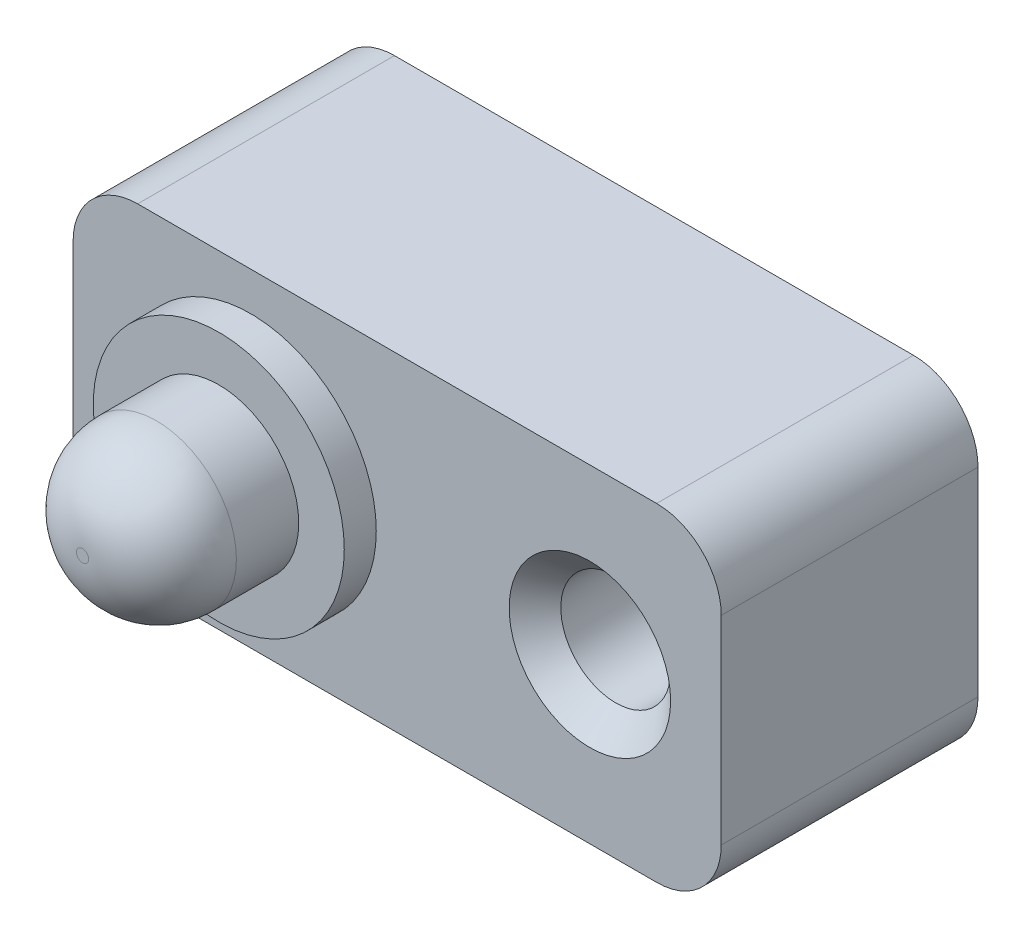
SolidWorks part; units mm, degrees
ref_plane "Front" through (0, 0, 0) normal (0, 0, 1) x (1, 0, 0)
ref_plane "Top" through (0, 0, 0) normal (0, 1, 0) x (1, 0, 0)
ref_plane "Right" through (0, 0, 0) normal (1, 0, 0) x (0, 0, -1)
sketch "Sketch1" plane through (0, 0, 0) normal (0, 0, 1) x (1, 0, 0)
  line L1 (0, 0) -> (20.066, 0)
  line L2 (0, 0) -> (0, 10.16)
  line L3 (0, 10.16) -> (20.066, 10.16)
  line L4 (20.066, 0) -> (20.066, 10.16)
  dimension "D1" = 20.066
  dimension "D2" = 10.16
extrude "Boss-Extrude1" add sketch "Sketch1" along normal blind 7.9502
sketch "Sketch2" plane through (0, 0, 7.9502) normal (0, 0, 1) x (1, 0, 0)
  line L0 (0, 10.16) -> (0, 0) construction
  line L1 (5.5, 10.16) -> (5.5, 0) construction
  line L2 (20.066, 10.16) -> (0, 10.16) construction
  line L3 (0, 0) -> (20.066, 0) construction
  circle A0 centre (5.5, 5.08) radius 3.8862
  dimension "D1" = 7.7724
  dimension "D2" = 5.5
extrude "Boss-Extrude2" add sketch "Sketch2" along normal blind 0.9906
sketch "Sketch3" plane through (0, 0, 8.9408) normal (0, 0, 1) x (1, 0, 0)
  circle A0 centre (5.5, 5.08) radius 2.4765
  dimension "D1" = 4.953
extrude "Boss-Extrude3" add sketch "Sketch3" along normal blind 4.2164
hole_wizard "CSK for M3 SFHCS1" positions "Sketch4" profile "Sketch5" countersink size "M3" standard "ANSI Metric" end condition through all
sketch "Sketch4" plane through (0, 0, 7.9502) normal (0, 0, 1) x (1, 0, 0)
  line L0 (16, 10.16) -> (16, 0) construction
  line L1 (20.066, 10.16) -> (0, 10.16) construction
  line L2 (0, 0) -> (20.066, 0) construction
  circle A0 centre (5.5, 5.08) radius 2.4765 construction
  point P0 (16, 5.08)
  dimension "D1" = 10.5
sketch "Sketch5" plane through (16, 5.08, 7.9502) normal (1, 0, 0) x (0, -1, 0)
  line L0 (0, 0) -> (0, 7.9502)
  line L1 (0, 7.9502) -> (1.7, 7.9502)
  line L2 (1.7, 7.9502) -> (1.7, 0.8)
  line L3 (1.7, 0.8) -> (2.5, 0)
  line L5 (2.5, 0) -> (0, 0)
  line L6 (-1.7, 0.8) -> (-2.5, 0) construction
  line L11 (0, -6.35) -> (0, 107.95) construction
  dimension "Thru Hole Dia." = 3.4
  dimension "Thru Hole Depth" = 7.9502
  dimension "Near C'Sink Dia." = 5
  dimension "Near C'Sink Angle" = 90
fillet "Fillet1" radius 2.286 1 edges at (7.9765, 5.08, 13.1572)
fillet "Fillet2" radius 2 4 edges at (0, 0, 3.9751) (0, 10.16, 3.9751) (20.066, 0, 3.9751) (20.066, 10.16, 3.9751)
